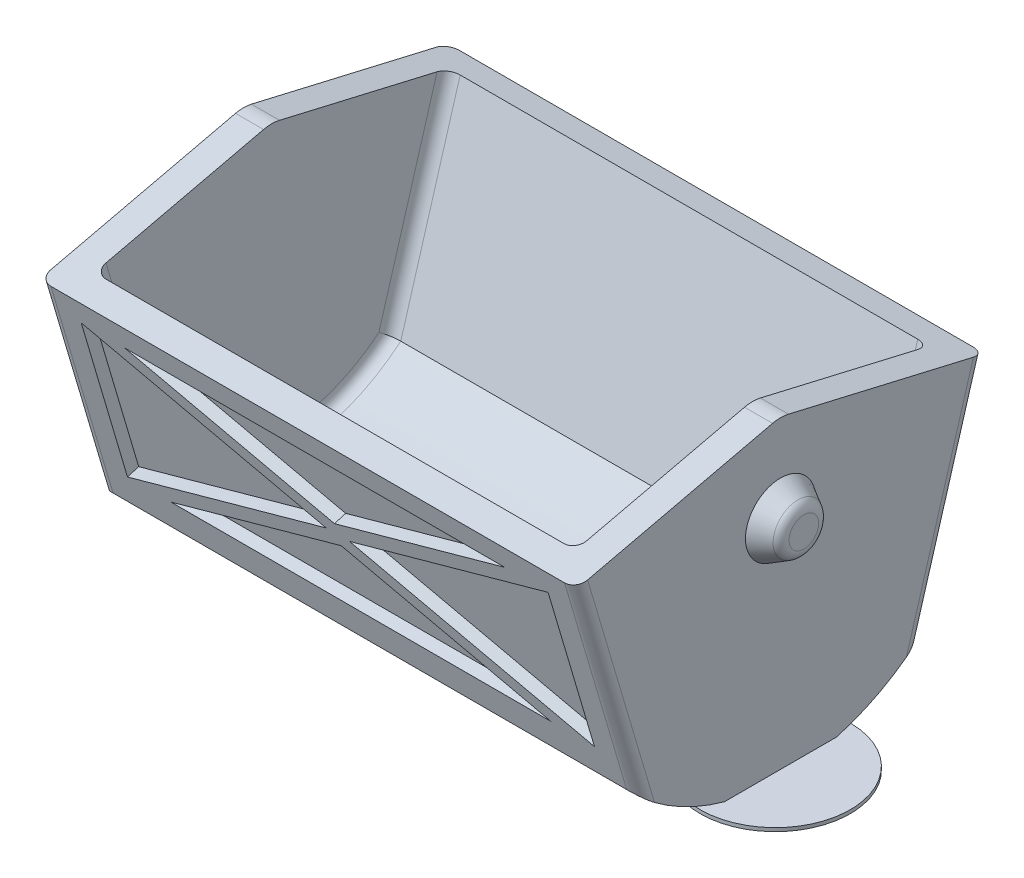
SolidWorks part; units mm, degrees
note: The reader was unsure of these and kept them because the rebuilt part matched: shared geometry of "Sketch2<2>".
material "ABS"
ref_plane "Front Plane" through (0, 0, 0) normal (0, 0, 1) x (1, 0, 0)
ref_plane "Top Plane" through (0, 0, 0) normal (0, 1, 0) x (1, 0, 0)
ref_plane "Right Plane" through (0, 0, 0) normal (1, 0, 0) x (0, 0, -1)
sketch "Sketch1" plane through (0, 0, 0) normal (1, 0, 0) x (0, 0, -1)
  line L0 (-12.1763, -9.5264) -> (-17.5, 8.4736)
  line L1 (-17.5, 8.4736) -> (-0.6812, 12.3952)
  line L2 (12.1763, -9.5264) -> (17.5, 8.4736)
  line L3 (17.5, 8.4736) -> (0.6812, 12.3952)
  line L4 (-17.5, 8.4736) -> (17.5, 8.4736) construction
  line L5 (-12.1763, -9.5264) -> (12.1763, -9.5264) construction
  arc A0 (12.1763, -9.5264) -> (-12.1763, -9.5264) centre (0, 3.7302) cw
  arc A1 (-0.6812, 12.3952) -> (0.6812, 12.3952) centre (0, 9.4736) cw
  point P7 (0, -9.5264)
  point P10 (0, 8.4736)
  dimension "D3" = 1
  dimension "D4" = 3
  dimension "D5" = 18
  dimension "D1" = 35
  dimension "D2" = 18
extrude "Boss-Extrude1" add sketch "Sketch1" along normal mid plane 46
shell "Shell1" thickness 2.4
sketch "Sketch2" plane through (0, 0, 0) normal (1, 0, 0) x (0, 0, -1)
  circle A0 centre (0, 5) radius 3
  dimension "D1" = 6
  dimension "D2" = 5
extrude "Boss-Extrude2" add sketch "Sketch2" along normal blind 2 draft 30 from surface at 23 starting at face at (23, 3.0033, 0)
extrude "Boss-Extrude3" add sketch "Sketch2<2>" against normal blind 2 draft 30 from surface at -23 starting at face at (-23, 3.0033, 0)
sketch "Sketch2<2>" plane through (0, 0, 0) normal (1, 0, 0) x (0, 0, -1) same geometry as "Sketch2"
fillet "Fillet1" radius 1 10 edges at (-20.6, 0.4179, 12.6147) (-20.6, 0.4179, -12.6147) (20.6, 0.4179, 12.6147) (20.6, 0.4179, -12.6147) (23, -0.5264, 14.8381) (-23, -0.5264, 14.8381) (-20.6, -11.8698, 0) (20.6, -11.8698, 0) (23, -0.5264, -14.8381) (-23, -0.5264, -14.8381)
ref_plane "Plane1" through (0, -4.0779, 13.7878) normal (0, -0.2836, 0.9589) x (1, 0, 0)
sketch "Sketch3" plane through (0, -99.3096, -14.3782) normal (0, 0.2836, -0.9589) x (1, 0, 0)
  line L0 (-20, -96.3096) -> (-1, -103.3096)
  line L1 (-20, -110.3096) -> (20, -110.3096) construction
  line L2 (-20, -110.3096) -> (-20, -96.3096)
  line L3 (-20, -96.3096) -> (20, -96.3096) construction
  line L4 (20, -110.3096) -> (20, -96.3096)
  line L5 (-20, -110.3096) -> (20, -96.3096) construction
  line L6 (-20, -96.3096) -> (20, -110.3096) construction
  line L7 (-1, -103.3096) -> (-20, -110.3096)
  line L8 (1, -103.3096) -> (20, -110.3096)
  line L9 (1, -103.3096) -> (20, -96.3096)
  line L10 (-16.2857, -96.3096) -> (16.2857, -96.3096)
  line L11 (16.2857, -96.3096) -> (0, -102.3096)
  line L12 (0, -102.3096) -> (-16.2857, -96.3096)
  line L13 (-16.2857, -110.3096) -> (16.2857, -110.3096)
  line L14 (16.2857, -110.3096) -> (0, -104.3096)
  line L15 (0, -104.3096) -> (-16.2857, -110.3096)
  point P0 (0, -103.3096)
  point P16 (0, -110.3096)
  point P17 (0, -96.3096)
  dimension "D1" = 40
  dimension "D2" = 14
  dimension "D3" = 2
  dimension "D4" = 2
extrude "Cut-Extrude1" cut sketch "Sketch3" along normal blind 1
mirror "Mirror1" about plane through (0, 0, 0) normal (0, 0, 1) of "Cut-Extrude1"
sketch "Sketch4" plane through (0, 0, 0) normal (1, 0, 0) x (0, 0, -1)
  line L1 (20.2517, -13.9185) -> (-20.2517, -13.9185)
  line L2 (20.2517, -13.9185) -> (20.2517, -22.3835)
  line L3 (20.2517, -22.3835) -> (-20.2517, -22.3835)
  line L4 (-20.2517, -13.9185) -> (-20.2517, -22.3835)
  line L5 (20.2517, -13.9185) -> (-20.2517, -22.3835) construction
  line L6 (20.2517, -22.3835) -> (-20.2517, -13.9185) construction
  point P0 (0, -18.151)
extrude "Cut-Extrude2" cut sketch "Sketch4" against normal mid plane 100
sketch "Sketch5" plane through (0, 0, 0) normal (0, 1, 0) x (1, 0, 0)
  line L0 (22.5524, 0) -> (-22.5524, 0) construction
  circle A0 centre (22.5524, 0) radius 6.4296
  circle A1 centre (-22.5524, 0) radius 6.4296
  point P4 (0, 0)
  point P5 (-25.1271, 0)
  point P7 (-22.5524, 0)
extrude "Boss-Extrude4" add sketch "Sketch5" along normal blind 0.3 from vertex
fillet "Fillet2" radius 1 2 edges at (25, 5, 1.8453) (-25, 5, 1.8453)
